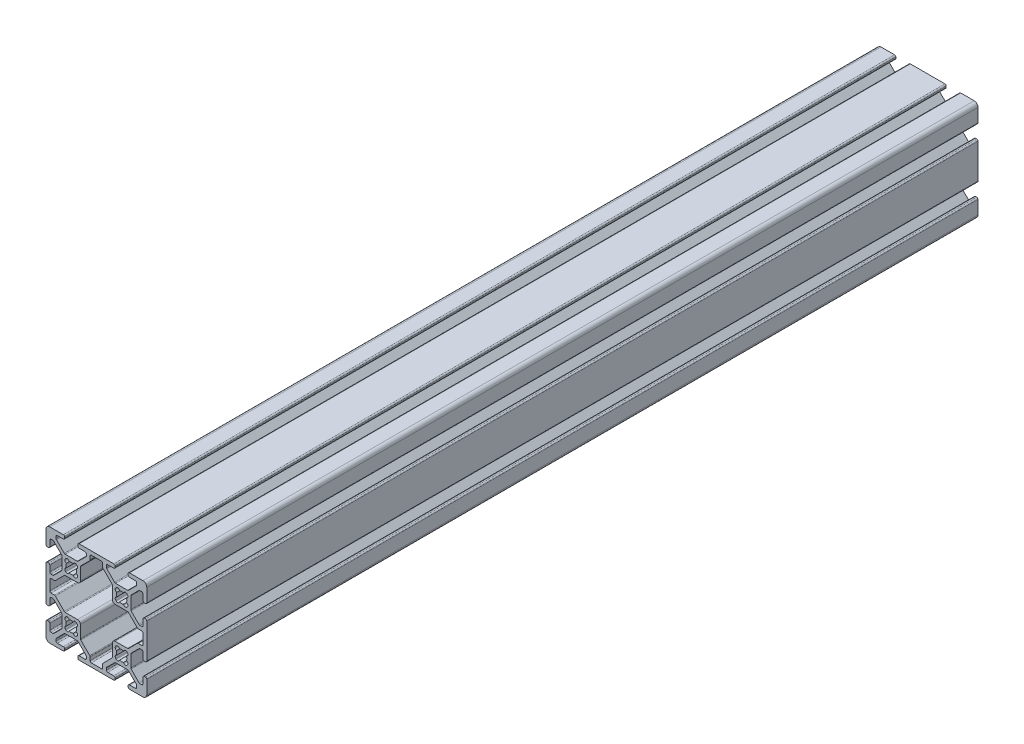
SolidWorks part; units mm, degrees
material "6105-T5 Aluminum"
ref_plane "Front Plane" through (0, 0, 0) normal (0, 0, 1) x (1, 0, 0)
ref_plane "Top Plane" through (0, 0, 0) normal (0, 1, 0) x (1, 0, 0)
ref_plane "Right Plane" through (0, 0, 0) normal (1, 0, 0) x (0, 0, -1)
sketch "Sketch1" plane through (0, 0, 0) normal (0, 0, 1) x (1, 0, 0)
  line L0 (-2.1249, 17.6955) -> (-2.3045, 17.8751)
  line L1 (-2.3045, 22.1249) -> (-2.1249, 22.3045)
  line L2 (2.1249, 22.3045) -> (2.3045, 22.1249)
  line L3 (2.3045, 17.8751) -> (2.1249, 17.6955)
  line L4 (-22.1249, 17.6955) -> (-22.3045, 17.8751)
  line L5 (-22.3045, 22.1249) -> (-22.1249, 22.3045)
  line L6 (-17.8751, 22.3045) -> (-17.6955, 22.1249)
  line L7 (-17.6955, 17.8751) -> (-17.8751, 17.6955)
  line L8 (-2.1249, -2.3045) -> (-2.3045, -2.1249)
  line L9 (-2.3045, 2.1249) -> (-2.1249, 2.3045)
  line L10 (2.1249, 2.3045) -> (2.3045, 2.1249)
  line L11 (2.3045, -2.1249) -> (2.1249, -2.3045)
  line L12 (-12.505, -7.992) -> (-12.505, -6.6448)
  line L13 (-12.6538, -6.2856) -> (-16.1962, -2.7431)
  line L14 (-16.345, -2.3839) -> (-16.345, 2.512)
  line L15 (-17.488, 3.655) -> (-22.3839, 3.655)
  line L16 (-22.7431, 3.8038) -> (-26.2856, 7.3462)
  line L17 (-26.6448, 7.495) -> (-27.992, 7.495)
  line L18 (-28.5, 8.003) -> (-28.5, 11.997)
  line L19 (-27.992, 12.505) -> (-26.6448, 12.505)
  line L20 (-26.2856, 12.6538) -> (-22.7431, 16.1962)
  line L21 (-22.3839, 16.345) -> (-17.488, 16.345)
  line L22 (-16.345, 17.488) -> (-16.345, 22.3839)
  line L23 (-16.1962, 22.7431) -> (-12.6538, 26.2856)
  line L24 (-12.505, 26.6448) -> (-12.505, 27.992)
  line L25 (-11.997, 28.5) -> (-8.003, 28.5)
  line L26 (-7.495, 27.992) -> (-7.495, 26.6448)
  line L27 (-7.3462, 26.2856) -> (-3.8038, 22.7431)
  line L28 (-3.655, 22.3839) -> (-3.655, 17.488)
  line L29 (-2.512, 16.345) -> (2.3839, 16.345)
  line L30 (2.7431, 16.1962) -> (6.2856, 12.6538)
  line L31 (6.6448, 12.505) -> (7.992, 12.505)
  line L32 (8.5, 11.997) -> (8.5, 8.003)
  line L33 (7.992, 7.495) -> (6.6448, 7.495)
  line L34 (6.2856, 7.3462) -> (2.7431, 3.8038)
  line L35 (2.3839, 3.655) -> (-2.512, 3.655)
  line L36 (-3.655, 2.512) -> (-3.655, -2.3839)
  line L37 (-3.8038, -2.7431) -> (-7.3462, -6.2856)
  line L38 (-7.495, -6.6448) -> (-7.495, -7.992)
  line L39 (-8.003, -8.5) -> (-11.997, -8.5)
  line L40 (-22.1249, -2.3045) -> (-22.3045, -2.1249)
  line L41 (-22.3045, 2.1249) -> (-22.1249, 2.3045)
  line L42 (-17.8751, 2.3045) -> (-17.6955, 2.1249)
  line L43 (-17.6955, -2.1249) -> (-17.8751, -2.3045)
  line L44 (-22.3839, -3.655) -> (-17.6161, -3.655)
  line L45 (-17.2569, -3.8038) -> (-14.1538, -6.9069)
  line L46 (-14.005, -7.2661) -> (-14.005, -7.992)
  line L47 (-14.513, -8.5) -> (-16.862, -8.5)
  line L48 (-17.37, -9.008) -> (-17.37, -9.492)
  line L49 (-16.862, -10) -> (-3.138, -10)
  line L50 (-2.63, -9.492) -> (-2.63, -9.008)
  line L51 (-3.138, -8.5) -> (-5.487, -8.5)
  line L52 (-5.995, -7.992) -> (-5.995, -7.2661)
  line L53 (-5.8462, -6.9069) -> (-2.7431, -3.8038)
  line L54 (-2.3839, -3.655) -> (2.3839, -3.655)
  line L55 (2.7431, -3.8038) -> (5.8462, -6.9069)
  line L56 (5.995, -7.2661) -> (5.995, -7.992)
  line L57 (5.487, -8.5) -> (3.138, -8.5)
  line L58 (2.63, -9.008) -> (2.63, -9.492)
  line L59 (3.138, -10) -> (8.5, -10)
  line L60 (10, -8.5) -> (10, -3.138)
  line L61 (9.492, -2.63) -> (9.008, -2.63)
  line L62 (8.5, -3.138) -> (8.5, -5.487)
  line L63 (7.992, -5.995) -> (7.2661, -5.995)
  line L64 (6.9069, -5.8462) -> (3.8038, -2.7431)
  line L65 (3.655, -2.3839) -> (3.655, 2.3839)
  line L66 (3.8038, 2.7431) -> (6.9069, 5.8462)
  line L67 (7.2661, 5.995) -> (7.992, 5.995)
  line L68 (8.5, 5.487) -> (8.5, 3.138)
  line L69 (9.008, 2.63) -> (9.492, 2.63)
  line L70 (10, 3.138) -> (10, 16.862)
  line L71 (9.492, 17.37) -> (9.008, 17.37)
  line L72 (8.5, 16.862) -> (8.5, 14.513)
  line L73 (7.992, 14.005) -> (7.2661, 14.005)
  line L74 (6.9069, 14.1538) -> (3.8038, 17.2569)
  line L75 (3.655, 17.6161) -> (3.655, 22.3839)
  line L76 (3.8038, 22.7431) -> (6.9069, 25.8462)
  line L77 (7.2661, 25.995) -> (7.992, 25.995)
  line L78 (8.5, 25.487) -> (8.5, 23.138)
  line L79 (9.008, 22.63) -> (9.492, 22.63)
  line L80 (10, 23.138) -> (10, 28.5)
  line L81 (8.5, 30) -> (3.138, 30)
  line L82 (2.63, 29.492) -> (2.63, 29.008)
  line L83 (3.138, 28.5) -> (5.487, 28.5)
  line L84 (5.995, 27.992) -> (5.995, 27.2661)
  line L85 (5.8462, 26.9069) -> (2.7431, 23.8038)
  line L86 (2.3839, 23.655) -> (-2.3839, 23.655)
  line L87 (-2.7431, 23.8038) -> (-5.8462, 26.9069)
  line L88 (-5.995, 27.2661) -> (-5.995, 27.992)
  line L89 (-5.487, 28.5) -> (-3.138, 28.5)
  line L90 (-2.63, 29.008) -> (-2.63, 29.492)
  line L91 (-3.138, 30) -> (-16.862, 30)
  line L92 (-17.37, 29.492) -> (-17.37, 29.008)
  line L93 (-16.862, 28.5) -> (-14.513, 28.5)
  line L94 (-14.005, 27.992) -> (-14.005, 27.2661)
  line L95 (-14.1538, 26.9069) -> (-17.2569, 23.8038)
  line L96 (-17.6161, 23.655) -> (-22.3839, 23.655)
  line L97 (-22.7431, 23.8038) -> (-25.8462, 26.9069)
  line L98 (-25.995, 27.2661) -> (-25.995, 27.992)
  line L99 (-25.487, 28.5) -> (-23.138, 28.5)
  line L100 (-22.63, 29.008) -> (-22.63, 29.492)
  line L101 (-23.138, 30) -> (-28.5, 30)
  line L102 (-30, 28.5) -> (-30, 23.138)
  line L103 (-29.492, 22.63) -> (-29.008, 22.63)
  line L104 (-28.5, 23.138) -> (-28.5, 25.487)
  line L105 (-27.992, 25.995) -> (-27.2661, 25.995)
  line L106 (-26.9069, 25.8462) -> (-23.8038, 22.7431)
  line L107 (-23.655, 22.3839) -> (-23.655, 17.6161)
  line L108 (-23.8038, 17.2569) -> (-26.9069, 14.1538)
  line L109 (-27.2661, 14.005) -> (-27.992, 14.005)
  line L110 (-28.5, 14.513) -> (-28.5, 16.862)
  line L111 (-29.008, 17.37) -> (-29.492, 17.37)
  line L112 (-30, 16.862) -> (-30, 3.138)
  line L113 (-29.492, 2.63) -> (-29.008, 2.63)
  line L114 (-28.5, 3.138) -> (-28.5, 5.487)
  line L115 (-27.992, 5.995) -> (-27.2661, 5.995)
  line L116 (-26.9069, 5.8462) -> (-23.8038, 2.7431)
  line L117 (-23.655, 2.3839) -> (-23.655, -2.3839)
  line L118 (-23.8038, -2.7431) -> (-26.9069, -5.8462)
  line L119 (-27.2661, -5.995) -> (-27.992, -5.995)
  line L120 (-28.5, -5.487) -> (-28.5, -3.138)
  line L121 (-29.008, -2.63) -> (-29.492, -2.63)
  line L122 (-30, -3.138) -> (-30, -8.5)
  line L123 (-28.5, -10) -> (-23.138, -10)
  line L124 (-22.63, -9.492) -> (-22.63, -9.008)
  line L125 (-23.138, -8.5) -> (-25.487, -8.5)
  line L126 (-25.995, -7.992) -> (-25.995, -7.2661)
  line L127 (-25.8462, -6.9069) -> (-22.7431, -3.8038)
  arc A0 (-1.9351, 19.196) -> (-2.3045, 17.8751) centre (-1.748, 18.4316) ccw
  arc A1 (-1.9351, 20.804) -> (-1.9351, 19.196) centre (0, 20) ccw
  arc A2 (-2.3045, 22.1249) -> (-1.9351, 20.804) centre (-1.748, 21.5684) ccw
  arc A3 (-0.804, 21.9351) -> (-2.1249, 22.3045) centre (-1.5684, 21.748) ccw
  arc A4 (0.804, 21.9351) -> (-0.804, 21.9351) centre (0, 20) ccw
  arc A5 (2.1249, 22.3045) -> (0.804, 21.9351) centre (1.5684, 21.748) ccw
  arc A6 (1.9351, 20.804) -> (2.3045, 22.1249) centre (1.748, 21.5684) ccw
  arc A7 (1.9351, 19.196) -> (1.9351, 20.804) centre (0, 20) ccw
  arc A8 (2.3045, 17.8751) -> (1.9351, 19.196) centre (1.748, 18.4316) ccw
  arc A9 (0.804, 18.0649) -> (2.1249, 17.6955) centre (1.5684, 18.252) ccw
  arc A10 (-0.804, 18.0649) -> (0.804, 18.0649) centre (0, 20) ccw
  arc A11 (-2.1249, 17.6955) -> (-0.804, 18.0649) centre (-1.5684, 18.252) ccw
  arc A12 (-21.9351, 19.196) -> (-22.3045, 17.8751) centre (-21.748, 18.4316) ccw
  arc A13 (-21.9351, 20.804) -> (-21.9351, 19.196) centre (-20, 20) ccw
  arc A14 (-22.3045, 22.1249) -> (-21.9351, 20.804) centre (-21.748, 21.5684) ccw
  arc A15 (-20.804, 21.9351) -> (-22.1249, 22.3045) centre (-21.5684, 21.748) ccw
  arc A16 (-19.196, 21.9351) -> (-20.804, 21.9351) centre (-20, 20) ccw
  arc A17 (-17.8751, 22.3045) -> (-19.196, 21.9351) centre (-18.4316, 21.748) ccw
  arc A18 (-18.0649, 20.804) -> (-17.6955, 22.1249) centre (-18.252, 21.5684) ccw
  arc A19 (-18.0649, 19.196) -> (-18.0649, 20.804) centre (-20, 20) ccw
  arc A20 (-17.6955, 17.8751) -> (-18.0649, 19.196) centre (-18.252, 18.4316) ccw
  arc A21 (-19.196, 18.0649) -> (-17.8751, 17.6955) centre (-18.4316, 18.252) ccw
  arc A22 (-20.804, 18.0649) -> (-19.196, 18.0649) centre (-20, 20) ccw
  arc A23 (-22.1249, 17.6955) -> (-20.804, 18.0649) centre (-21.5684, 18.252) ccw
  arc A24 (-1.9351, -0.804) -> (-2.3045, -2.1249) centre (-1.748, -1.5684) ccw
  arc A25 (-1.9351, 0.804) -> (-1.9351, -0.804) centre (0, 0) ccw
  arc A26 (-2.3045, 2.1249) -> (-1.9351, 0.804) centre (-1.748, 1.5684) ccw
  arc A27 (-0.804, 1.9351) -> (-2.1249, 2.3045) centre (-1.5684, 1.748) ccw
  arc A28 (0.804, 1.9351) -> (-0.804, 1.9351) centre (0, 0) ccw
  arc A29 (2.1249, 2.3045) -> (0.804, 1.9351) centre (1.5684, 1.748) ccw
  arc A30 (1.9351, 0.804) -> (2.3045, 2.1249) centre (1.748, 1.5684) ccw
  arc A31 (1.9351, -0.804) -> (1.9351, 0.804) centre (0, 0) ccw
  arc A32 (2.3045, -2.1249) -> (1.9351, -0.804) centre (1.748, -1.5684) ccw
  arc A33 (0.804, -1.9351) -> (2.1249, -2.3045) centre (1.5684, -1.748) ccw
  arc A34 (-0.804, -1.9351) -> (0.804, -1.9351) centre (0, 0) ccw
  arc A35 (-2.1249, -2.3045) -> (-0.804, -1.9351) centre (-1.5684, -1.748) ccw
  arc A36 (-12.505, -7.992) -> (-11.997, -8.5) centre (-11.997, -7.992) ccw
  arc A37 (-12.505, -6.6448) -> (-12.6538, -6.2856) centre (-13.013, -6.6448) ccw
  arc A38 (-16.345, -2.3839) -> (-16.1962, -2.7431) centre (-15.837, -2.3839) ccw
  arc A39 (-16.345, 2.512) -> (-17.488, 3.655) centre (-17.488, 2.512) ccw
  arc A40 (-22.7431, 3.8038) -> (-22.3839, 3.655) centre (-22.3839, 4.163) ccw
  arc A41 (-26.2856, 7.3462) -> (-26.6448, 7.495) centre (-26.6448, 6.987) ccw
  arc A42 (-28.5, 8.003) -> (-27.992, 7.495) centre (-27.992, 8.003) ccw
  arc A43 (-27.992, 12.505) -> (-28.5, 11.997) centre (-27.992, 11.997) ccw
  arc A44 (-26.6448, 12.505) -> (-26.2856, 12.6538) centre (-26.6448, 13.013) ccw
  arc A45 (-22.3839, 16.345) -> (-22.7431, 16.1962) centre (-22.3839, 15.837) ccw
  arc A46 (-17.488, 16.345) -> (-16.345, 17.488) centre (-17.488, 17.488) ccw
  arc A47 (-16.1962, 22.7431) -> (-16.345, 22.3839) centre (-15.837, 22.3839) ccw
  arc A48 (-12.6538, 26.2856) -> (-12.505, 26.6448) centre (-13.013, 26.6448) ccw
  arc A49 (-11.997, 28.5) -> (-12.505, 27.992) centre (-11.997, 27.992) ccw
  arc A50 (-7.495, 27.992) -> (-8.003, 28.5) centre (-8.003, 27.992) ccw
  arc A51 (-7.495, 26.6448) -> (-7.3462, 26.2856) centre (-6.987, 26.6448) ccw
  arc A52 (-3.655, 22.3839) -> (-3.8038, 22.7431) centre (-4.163, 22.3839) ccw
  arc A53 (-3.655, 17.488) -> (-2.512, 16.345) centre (-2.512, 17.488) ccw
  arc A54 (2.7431, 16.1962) -> (2.3839, 16.345) centre (2.3839, 15.837) ccw
  arc A55 (6.2856, 12.6538) -> (6.6448, 12.505) centre (6.6448, 13.013) ccw
  arc A56 (8.5, 11.997) -> (7.992, 12.505) centre (7.992, 11.997) ccw
  arc A57 (7.992, 7.495) -> (8.5, 8.003) centre (7.992, 8.003) ccw
  arc A58 (6.6448, 7.495) -> (6.2856, 7.3462) centre (6.6448, 6.987) ccw
  arc A59 (2.3839, 3.655) -> (2.7431, 3.8038) centre (2.3839, 4.163) ccw
  arc A60 (-2.512, 3.655) -> (-3.655, 2.512) centre (-2.512, 2.512) ccw
  arc A61 (-3.8038, -2.7431) -> (-3.655, -2.3839) centre (-4.163, -2.3839) ccw
  arc A62 (-7.3462, -6.2856) -> (-7.495, -6.6448) centre (-6.987, -6.6448) ccw
  arc A63 (-8.003, -8.5) -> (-7.495, -7.992) centre (-8.003, -7.992) ccw
  arc A64 (-21.9351, -0.804) -> (-22.3045, -2.1249) centre (-21.748, -1.5684) ccw
  arc A65 (-21.9351, 0.804) -> (-21.9351, -0.804) centre (-20, 0) ccw
  arc A66 (-22.3045, 2.1249) -> (-21.9351, 0.804) centre (-21.748, 1.5684) ccw
  arc A67 (-20.804, 1.9351) -> (-22.1249, 2.3045) centre (-21.5684, 1.748) ccw
  arc A68 (-19.196, 1.9351) -> (-20.804, 1.9351) centre (-20, 0) ccw
  arc A69 (-17.8751, 2.3045) -> (-19.196, 1.9351) centre (-18.4316, 1.748) ccw
  arc A70 (-18.0649, 0.804) -> (-17.6955, 2.1249) centre (-18.252, 1.5684) ccw
  arc A71 (-18.0649, -0.804) -> (-18.0649, 0.804) centre (-20, 0) ccw
  arc A72 (-17.6955, -2.1249) -> (-18.0649, -0.804) centre (-18.252, -1.5684) ccw
  arc A73 (-19.196, -1.9351) -> (-17.8751, -2.3045) centre (-18.4316, -1.748) ccw
  arc A74 (-20.804, -1.9351) -> (-19.196, -1.9351) centre (-20, 0) ccw
  arc A75 (-22.1249, -2.3045) -> (-20.804, -1.9351) centre (-21.5684, -1.748) ccw
  arc A76 (-22.3839, -3.655) -> (-22.7431, -3.8038) centre (-22.3839, -4.163) ccw
  arc A77 (-17.2569, -3.8038) -> (-17.6161, -3.655) centre (-17.6161, -4.163) ccw
  arc A78 (-14.005, -7.2661) -> (-14.1538, -6.9069) centre (-14.513, -7.2661) ccw
  arc A79 (-14.513, -8.5) -> (-14.005, -7.992) centre (-14.513, -7.992) ccw
  arc A80 (-16.862, -8.5) -> (-17.37, -9.008) centre (-16.862, -9.008) ccw
  arc A81 (-17.37, -9.492) -> (-16.862, -10) centre (-16.862, -9.492) ccw
  arc A82 (-3.138, -10) -> (-2.63, -9.492) centre (-3.138, -9.492) ccw
  arc A83 (-2.63, -9.008) -> (-3.138, -8.5) centre (-3.138, -9.008) ccw
  arc A84 (-5.995, -7.992) -> (-5.487, -8.5) centre (-5.487, -7.992) ccw
  arc A85 (-5.8462, -6.9069) -> (-5.995, -7.2661) centre (-5.487, -7.2661) ccw
  arc A86 (-2.3839, -3.655) -> (-2.7431, -3.8038) centre (-2.3839, -4.163) ccw
  arc A87 (2.7431, -3.8038) -> (2.3839, -3.655) centre (2.3839, -4.163) ccw
  arc A88 (5.995, -7.2661) -> (5.8462, -6.9069) centre (5.487, -7.2661) ccw
  arc A89 (5.487, -8.5) -> (5.995, -7.992) centre (5.487, -7.992) ccw
  arc A90 (3.138, -8.5) -> (2.63, -9.008) centre (3.138, -9.008) ccw
  arc A91 (2.63, -9.492) -> (3.138, -10) centre (3.138, -9.492) ccw
  arc A92 (8.5, -10) -> (10, -8.5) centre (8.5, -8.5) ccw
  arc A93 (10, -3.138) -> (9.492, -2.63) centre (9.492, -3.138) ccw
  arc A94 (9.008, -2.63) -> (8.5, -3.138) centre (9.008, -3.138) ccw
  arc A95 (7.992, -5.995) -> (8.5, -5.487) centre (7.992, -5.487) ccw
  arc A96 (6.9069, -5.8462) -> (7.2661, -5.995) centre (7.2661, -5.487) ccw
  arc A97 (3.655, -2.3839) -> (3.8038, -2.7431) centre (4.163, -2.3839) ccw
  arc A98 (3.8038, 2.7431) -> (3.655, 2.3839) centre (4.163, 2.3839) ccw
  arc A99 (7.2661, 5.995) -> (6.9069, 5.8462) centre (7.2661, 5.487) ccw
  arc A100 (8.5, 5.487) -> (7.992, 5.995) centre (7.992, 5.487) ccw
  arc A101 (8.5, 3.138) -> (9.008, 2.63) centre (9.008, 3.138) ccw
  arc A102 (9.492, 2.63) -> (10, 3.138) centre (9.492, 3.138) ccw
  arc A103 (10, 16.862) -> (9.492, 17.37) centre (9.492, 16.862) ccw
  arc A104 (9.008, 17.37) -> (8.5, 16.862) centre (9.008, 16.862) ccw
  arc A105 (7.992, 14.005) -> (8.5, 14.513) centre (7.992, 14.513) ccw
  arc A106 (6.9069, 14.1538) -> (7.2661, 14.005) centre (7.2661, 14.513) ccw
  arc A107 (3.655, 17.6161) -> (3.8038, 17.2569) centre (4.163, 17.6161) ccw
  arc A108 (3.8038, 22.7431) -> (3.655, 22.3839) centre (4.163, 22.3839) ccw
  arc A109 (7.2661, 25.995) -> (6.9069, 25.8462) centre (7.2661, 25.487) ccw
  arc A110 (8.5, 25.487) -> (7.992, 25.995) centre (7.992, 25.487) ccw
  arc A111 (8.5, 23.138) -> (9.008, 22.63) centre (9.008, 23.138) ccw
  arc A112 (9.492, 22.63) -> (10, 23.138) centre (9.492, 23.138) ccw
  arc A113 (10, 28.5) -> (8.5, 30) centre (8.5, 28.5) ccw
  arc A114 (3.138, 30) -> (2.63, 29.492) centre (3.138, 29.492) ccw
  arc A115 (2.63, 29.008) -> (3.138, 28.5) centre (3.138, 29.008) ccw
  arc A116 (5.995, 27.992) -> (5.487, 28.5) centre (5.487, 27.992) ccw
  arc A117 (5.8462, 26.9069) -> (5.995, 27.2661) centre (5.487, 27.2661) ccw
  arc A118 (2.3839, 23.655) -> (2.7431, 23.8038) centre (2.3839, 24.163) ccw
  arc A119 (-2.7431, 23.8038) -> (-2.3839, 23.655) centre (-2.3839, 24.163) ccw
  arc A120 (-5.995, 27.2661) -> (-5.8462, 26.9069) centre (-5.487, 27.2661) ccw
  arc A121 (-5.487, 28.5) -> (-5.995, 27.992) centre (-5.487, 27.992) ccw
  arc A122 (-3.138, 28.5) -> (-2.63, 29.008) centre (-3.138, 29.008) ccw
  arc A123 (-2.63, 29.492) -> (-3.138, 30) centre (-3.138, 29.492) ccw
  arc A124 (-16.862, 30) -> (-17.37, 29.492) centre (-16.862, 29.492) ccw
  arc A125 (-17.37, 29.008) -> (-16.862, 28.5) centre (-16.862, 29.008) ccw
  arc A126 (-14.005, 27.992) -> (-14.513, 28.5) centre (-14.513, 27.992) ccw
  arc A127 (-14.1538, 26.9069) -> (-14.005, 27.2661) centre (-14.513, 27.2661) ccw
  arc A128 (-17.6161, 23.655) -> (-17.2569, 23.8038) centre (-17.6161, 24.163) ccw
  arc A129 (-22.7431, 23.8038) -> (-22.3839, 23.655) centre (-22.3839, 24.163) ccw
  arc A130 (-25.995, 27.2661) -> (-25.8462, 26.9069) centre (-25.487, 27.2661) ccw
  arc A131 (-25.487, 28.5) -> (-25.995, 27.992) centre (-25.487, 27.992) ccw
  arc A132 (-23.138, 28.5) -> (-22.63, 29.008) centre (-23.138, 29.008) ccw
  arc A133 (-22.63, 29.492) -> (-23.138, 30) centre (-23.138, 29.492) ccw
  arc A134 (-28.5, 30) -> (-30, 28.5) centre (-28.5, 28.5) ccw
  arc A135 (-30, 23.138) -> (-29.492, 22.63) centre (-29.492, 23.138) ccw
  arc A136 (-29.008, 22.63) -> (-28.5, 23.138) centre (-29.008, 23.138) ccw
  arc A137 (-27.992, 25.995) -> (-28.5, 25.487) centre (-27.992, 25.487) ccw
  arc A138 (-26.9069, 25.8462) -> (-27.2661, 25.995) centre (-27.2661, 25.487) ccw
  arc A139 (-23.655, 22.3839) -> (-23.8038, 22.7431) centre (-24.163, 22.3839) ccw
  arc A140 (-23.8038, 17.2569) -> (-23.655, 17.6161) centre (-24.163, 17.6161) ccw
  arc A141 (-27.2661, 14.005) -> (-26.9069, 14.1538) centre (-27.2661, 14.513) ccw
  arc A142 (-28.5, 14.513) -> (-27.992, 14.005) centre (-27.992, 14.513) ccw
  arc A143 (-28.5, 16.862) -> (-29.008, 17.37) centre (-29.008, 16.862) ccw
  arc A144 (-29.492, 17.37) -> (-30, 16.862) centre (-29.492, 16.862) ccw
  arc A145 (-30, 3.138) -> (-29.492, 2.63) centre (-29.492, 3.138) ccw
  arc A146 (-29.008, 2.63) -> (-28.5, 3.138) centre (-29.008, 3.138) ccw
  arc A147 (-27.992, 5.995) -> (-28.5, 5.487) centre (-27.992, 5.487) ccw
  arc A148 (-26.9069, 5.8462) -> (-27.2661, 5.995) centre (-27.2661, 5.487) ccw
  arc A149 (-23.655, 2.3839) -> (-23.8038, 2.7431) centre (-24.163, 2.3839) ccw
  arc A150 (-23.8038, -2.7431) -> (-23.655, -2.3839) centre (-24.163, -2.3839) ccw
  arc A151 (-27.2661, -5.995) -> (-26.9069, -5.8462) centre (-27.2661, -5.487) ccw
  arc A152 (-28.5, -5.487) -> (-27.992, -5.995) centre (-27.992, -5.487) ccw
  arc A153 (-28.5, -3.138) -> (-29.008, -2.63) centre (-29.008, -3.138) ccw
  arc A154 (-29.492, -2.63) -> (-30, -3.138) centre (-29.492, -3.138) ccw
  arc A155 (-30, -8.5) -> (-28.5, -10) centre (-28.5, -8.5) ccw
  arc A156 (-23.138, -10) -> (-22.63, -9.492) centre (-23.138, -9.492) ccw
  arc A157 (-22.63, -9.008) -> (-23.138, -8.5) centre (-23.138, -9.008) ccw
  arc A158 (-25.995, -7.992) -> (-25.487, -8.5) centre (-25.487, -7.992) ccw
  arc A159 (-25.8462, -6.9069) -> (-25.995, -7.2661) centre (-25.487, -7.2661) ccw
extrude "Extrude1" add sketch "Sketch1" against normal blind 330
